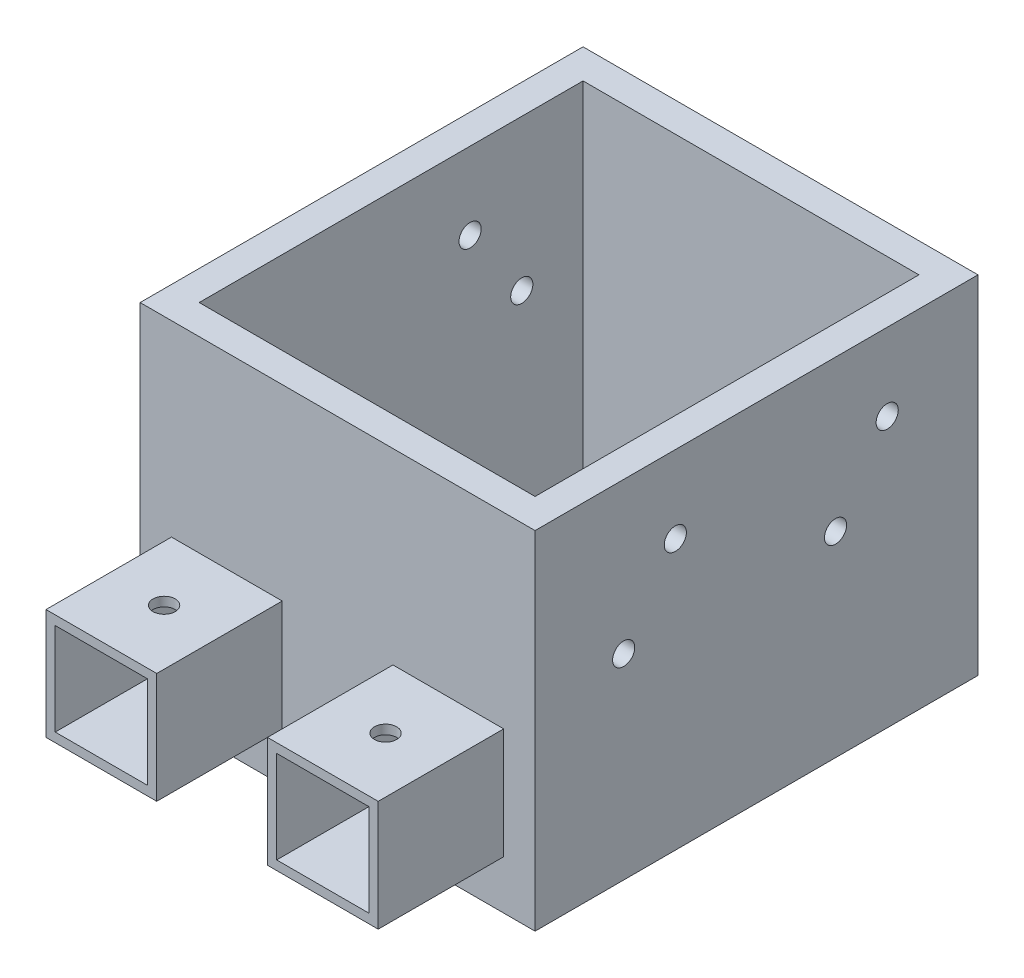
SolidWorks part; units mm, degrees
ref_plane "Front Plane" through (0, 0, 0) normal (0, 0, 1) x (1, 0, 0)
ref_plane "Top Plane" through (0, 0, 0) normal (0, 1, 0) x (1, 0, 0)
ref_plane "Right Plane" through (0, 0, 0) normal (1, 0, 0) x (0, 0, -1)
sketch "Sketch1" plane through (0, 0, 0) normal (0, 1, 0) x (1, 0, 0)
  line L1 (-26.75, 30) -> (26.75, 30)
  line L2 (-26.75, 30) -> (-26.75, -30)
  line L3 (-26.75, -30) -> (26.75, -30)
  line L4 (26.75, 30) -> (26.75, -30)
  line L5 (-26.75, 30) -> (26.75, -30) construction
  line L6 (-26.75, -30) -> (26.75, 30) construction
  line L7 (-22.75, 26) -> (22.75, 26)
  line L8 (-22.75, 26) -> (-22.75, -26)
  line L9 (-22.75, -26) -> (22.75, -26)
  line L10 (22.75, 26) -> (22.75, -26)
  line L11 (-22.75, 26) -> (22.75, -26) construction
  line L12 (-22.75, -26) -> (22.75, 26) construction
  point P0 (0, 0)
  point P6 (0, 0)
  dimension "D1" = 45.5
  dimension "D2" = 4
  dimension "D3" = 4
extrude "Boss-Extrude1" add sketch "Sketch1" along normal blind 47
sketch "Sketch3" plane through (-26.75, 0, 0) normal (-1, 0, 0) x (0, 0, 1)
  line L0 (-30, 47) -> (30, 47) construction
  circle A0 centre (18, 36.55) radius 1.5
  circle A1 centre (11, 26.55) radius 1.5
  dimension "D1" = 3
  dimension "D3" = 3
  dimension "D2" = 10.45
  dimension "D4" = 10
  dimension "D5" = 7
  dimension "D6" = 8
extrude "Cut-Extrude1" cut sketch "Sketch3" against normal blind 4 and the other way through all
pattern_linear "LPattern1" count 2 spacing 28.7 along (0, 0, -1) of "Cut-Extrude1"
sketch "Sketch4" plane through (26.75, 0, 0) normal (1, 0, 0) x (0, 0, -1)
  line L0 (-30, 47) -> (30, 47) construction
  circle A0 centre (-11, 36.55) radius 1.5
  circle A1 centre (-18, 26.55) radius 1.5
  dimension "D1" = 3
  dimension "D2" = 3
  dimension "D3" = 10
  dimension "D4" = 7
  dimension "D5" = 10.45
  dimension "D6" = 8
extrude "Cut-Extrude2" cut sketch "Sketch4" against normal blind 4
pattern_linear "LPattern2" count 2 spacing 28.7 along (0, 0, -1) of "Cut-Extrude2"
sketch "Sketch5" plane through (0, 0, 30) normal (0, 0, 1) x (1, 0, 0)
  line L0 (26.75, 47) -> (26.75, 0) construction
  line L1 (-22.5, 21.61) -> (-7.5, 21.61)
  line L2 (-22.5, 21.61) -> (-22.5, 6.61)
  line L3 (-22.5, 6.61) -> (-7.5, 6.61)
  line L4 (-7.5, 21.61) -> (-7.5, 6.61)
  line L5 (-22.5, 21.61) -> (-7.5, 6.61) construction
  line L6 (-22.5, 6.61) -> (-7.5, 21.61) construction
  line L7 (7.5, 21.61) -> (22.5, 21.61)
  line L8 (7.5, 21.61) -> (7.5, 6.61)
  line L9 (7.5, 6.61) -> (22.5, 6.61)
  line L10 (22.5, 21.61) -> (22.5, 6.61)
  line L11 (7.5, 21.61) -> (22.5, 6.61) construction
  line L12 (7.5, 6.61) -> (22.5, 21.61) construction
  line L13 (-26.75, 0) -> (26.75, 0) construction
  line L14 (-26.75, 47) -> (-26.75, 0) construction
  line L15 (8.75, 20.36) -> (21.25, 20.36)
  line L17 (8.75, 20.36) -> (8.75, 7.86)
  line L18 (8.75, 7.86) -> (21.25, 7.86)
  line L19 (21.25, 20.36) -> (21.25, 7.86)
  line L20 (8.75, 20.36) -> (21.25, 7.86) construction
  line L21 (8.75, 7.86) -> (21.25, 20.36) construction
  line L22 (-21.25, 20.36) -> (-8.75, 20.36)
  line L23 (-21.25, 20.36) -> (-21.25, 7.86)
  line L24 (-21.25, 7.86) -> (-8.75, 7.86)
  line L25 (-8.75, 20.36) -> (-8.75, 7.86)
  line L26 (-21.25, 20.36) -> (-8.75, 7.86) construction
  line L27 (-21.25, 7.86) -> (-8.75, 20.36) construction
  point P0 (-15, 14.11)
  point P5 (15, 14.11)
  point P16 (-15, 14.11)
  point P18 (15, 14.11)
  dimension "D1" = 4.25
  dimension "D2" = 4.25
  dimension "D3" = 15
  dimension "D5" = 12.5
  dimension "D4" = 6.61
extrude "Boss-Extrude2" add sketch "Sketch5" along normal blind 17
sketch "Sketch6" plane through (0, 21.61, 0) normal (0, 1, 0) x (1, 0, 0)
  line L1 (-7.5, -47) -> (-7.5, -30) construction
  line L2 (-7.5, -47) -> (-22.5, -47) construction
  line L3 (22.5, -47) -> (22.5, -30) construction
  line L4 (22.5, -47) -> (7.5, -47) construction
  circle A0 centre (-15, -38.5) radius 1.5
  circle A1 centre (15, -38.5) radius 1.5
  point P6 (-7.5, -38.5)
  point P11 (-15, -47)
  point P14 (22.5, -38.5)
  point P18 (15, -47)
  dimension "D1" = 3
  dimension "D2" = 3
extrude "Cut-Extrude3" cut sketch "Sketch6" against normal through all
equation "\"var1\"=4.25"
equation "\"D1@Sketch5\"=\"var1\""
equation "\"D2@Sketch5\"=\"var1\""
